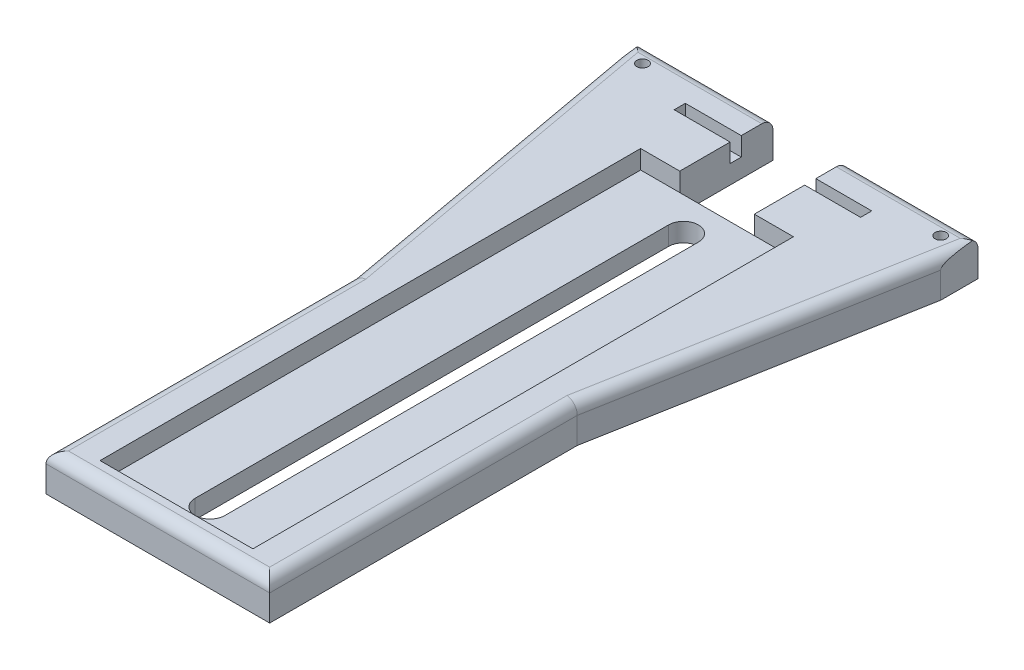
SolidWorks part; units mm, degrees
ref_plane "Front Plane" through (0, 0, 0) normal (0, 0, 1) x (1, 0, 0)
ref_plane "Top Plane" through (0, 0, 0) normal (0, 1, 0) x (1, 0, 0)
ref_plane "Right Plane" through (0, 0, 0) normal (1, 0, 0) x (0, 0, -1)
sketch "Sketch1" plane through (0, 0, 0) normal (0, 1, 0) x (1, 0, 0)
  line L0 (0, 0) -> (-45, 0)
  line L1 (-45, 0) -> (-45, -10)
  line L3 (-30, -92.5) -> (-30, -175)
  line L4 (-30, -175) -> (0, -175)
  line L5 (0, -175) -> (0, -165)
  line L6 (0, -34) -> (0, -161) construction
  line L7 (4, -34) -> (4, -161)
  line L8 (-4, -34) -> (-4, -161)
  line L9 (0, -30) -> (0, 0)
  line L10 (-45, -10) -> (-30, -92.5)
  arc A0 (4, -34) -> (-4, -34) centre (0, -34) ccw
  arc A1 (-4, -161) -> (4, -161) centre (0, -161) ccw
  circle A2 centre (-40, -5) radius 1.5
  point P9 (0, -97.5)
  dimension "D5" = 4
  dimension "D8" = 3
  dimension "D1" = 45
  dimension "D2" = 175
  dimension "D3" = 30
  dimension "D4" = 10
  dimension "D6" = 30
  dimension "D7" = 10
  dimension "D9" = 5
  dimension "D10" = 40
  dimension "D11" = 82.5
extrude "Boss-Extrude1" add sketch "Sketch1" along normal blind 10
sketch "Sketch2" plane through (0, 10, 0) normal (0, 1, 0) x (1, 0, 0)
  line L5 (0, 0) -> (-45, 0) construction
  line L6 (0, -25) -> (-20.5, -25)
  line L7 (0, -25) -> (0, -170)
  line L8 (0, -170) -> (-20.5, -170)
  line L9 (-20.5, -25) -> (-20.5, -170)
  line L10 (-30, -175) -> (0, -175) construction
  dimension "D1" = 25
  dimension "D2" = 20.5
  dimension "D3" = 5
extrude "Cut-Extrude1" cut sketch "Sketch2" against normal blind 5
mirror "Mirror1" about plane through (0, 0, 0) normal (1, 0, 0) of "Cut-Extrude1", "Boss-Extrude1"
sketch "Sketch3" plane through (0, 10, 0) normal (0, 1, 0) x (1, 0, 0)
  line L0 (45, 0) -> (-45, 0) construction
  line L1 (-10, 0) -> (10, 0)
  line L2 (-10, 0) -> (-10, -25)
  line L3 (-10, -25) -> (10, -25)
  line L4 (10, 0) -> (10, -25)
  line L5 (20.5, -25) -> (-20.5, -25) construction
  dimension "D1" = 10
  dimension "D2" = 20
extrude "Cut-Extrude2" cut sketch "Sketch3" against normal through all
sketch "Sketch4" plane through (0, 10, 0) normal (0, 1, 0) x (1, 0, 0)
  line L0 (45, 0) -> (10, 0) construction
  line L1 (-25, -8.5) -> (25, -8.5)
  line L2 (-25, -8.5) -> (-25, -11.5)
  line L3 (-25, -11.5) -> (25, -11.5)
  line L4 (25, -8.5) -> (25, -11.5)
  dimension "D1" = 3
  dimension "D2" = 50
  dimension "D3" = 25
  dimension "D4" = 8.5
extrude "Cut-Extrude3" cut sketch "Sketch4" against normal blind 5
fillet "Fillet1" radius 3 9 edges at (-27.5, 10, 0) (27.5, 10, 0) (-45, 10, 5) (-37.5, 10, 51.25) (-30, 10, 133.75) (0, 10, 175) (30, 10, 133.75) (37.5, 10, 51.25) (45, 10, 5)
sketch "Sketch6" plane through (0, 0, 0) normal (0, -1, 0) x (1, 0, 0)
  line L1 (-37.1472, 4.0719) -> (-37.7698, 7.0066)
  line L2 (-37.7698, 7.0066) -> (-40.6227, 7.9347)
  line L3 (-40.6227, 7.9347) -> (-42.8528, 5.9281)
  line L4 (-42.8528, 5.9281) -> (-42.2302, 2.9934)
  line L5 (-42.2302, 2.9934) -> (-39.3773, 2.0653)
  line L6 (-39.3773, 2.0653) -> (-37.1472, 4.0719)
  line L7 (41.9745, 2.7414) -> (42.9433, 5.5807)
  line L8 (42.9433, 5.5807) -> (40.9687, 7.8393)
  line L9 (40.9687, 7.8393) -> (38.0255, 7.2586)
  line L10 (38.0255, 7.2586) -> (37.0567, 4.4193)
  line L11 (37.0567, 4.4193) -> (39.0313, 2.1607)
  line L12 (39.0313, 2.1607) -> (41.9745, 2.7414)
  circle A0 centre (40, 5) radius 3
  circle A1 centre (-40, 5) radius 3
  circle A2 centre (-40, 5) radius 2.5981 construction
  circle A3 centre (40, 5) radius 2.5981 construction
  circle M24 centre (-40, 5) radius 1.5
  circle M25 centre (40, 5) radius 1.5
  dimension "D1" = 6
  dimension "D2" = 6
extrude "Cut-Extrude4" cut sketch "Sketch6" against normal blind 5 contours L5 L6 L1 L2 L3 L4 M24 | L11 L12 L7 L8 L9 L10 M25
chamfer "Chamfer2" distance 1 angle 45 12 edges at (38.044, 5, 3.29) (40.5029, 5, 2.4511) (42.4589, 5, 4.161) (41.956, 5, 6.71) (39.4971, 5, 7.5489) (37.5411, 5, 5.839) (-42.5415, 5, 4.4608) (-40.8038, 5, 2.5294) (-38.2623, 5, 3.0686) (-37.4585, 5, 5.5392) (-39.1962, 5, 7.4706) (-41.7377, 5, 6.9314)
